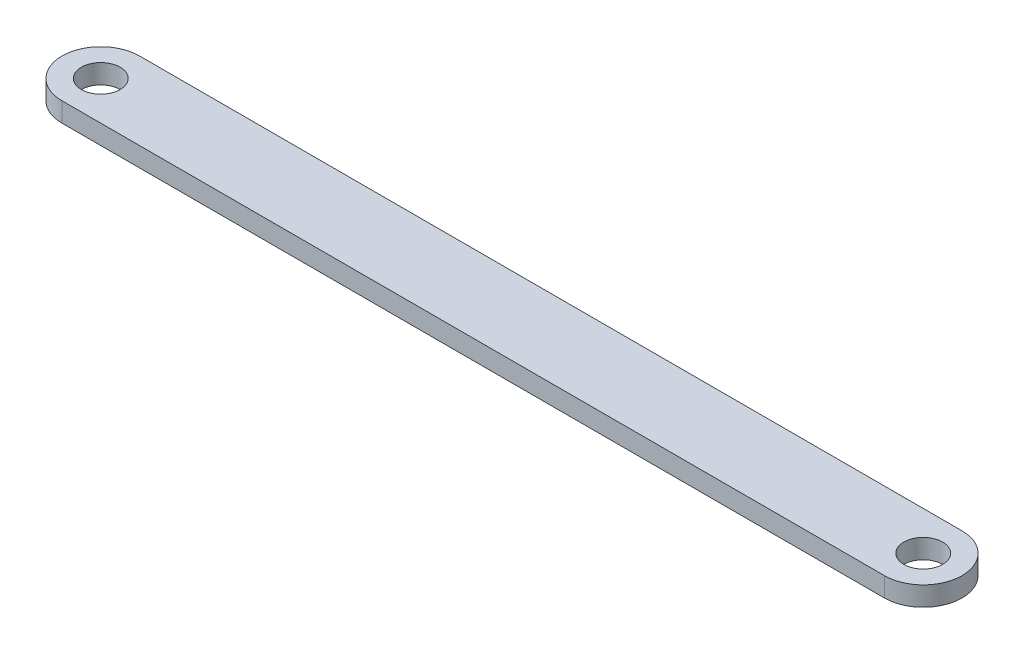
SolidWorks part; units mm, degrees
ref_plane "Ön Düzlem" through (0, 0, 0) normal (0, 0, 1) x (1, 0, 0)
ref_plane "Üst Düzlem" through (0, 0, 0) normal (0, 1, 0) x (1, 0, 0)
ref_plane "Sağ Düzlem" through (0, 0, 0) normal (1, 0, 0) x (0, 0, -1)
sketch "Sketch1" plane through (0, 0, 0) normal (0, 1, 0) x (1, 0, 0)
  line L0 (-106, 0) -> (106, 0) construction
  line L1 (-106, 10) -> (106, 10)
  line L2 (-106, -10) -> (106, -10)
  arc A0 (-106, 10) -> (-106, -10) centre (-106, 0) ccw
  arc A1 (106, -10) -> (106, 10) centre (106, 0) ccw
  circle A2 centre (-106, 0) radius 5
  circle A3 centre (106, 0) radius 5
  point P2 (0, 0)
  dimension "D1" = 10
  dimension "D3" = 10
  dimension "D4" = 10
  dimension "D2" = 212
extrude "Boss-Extrude1" add sketch "Sketch1" along normal blind 5
